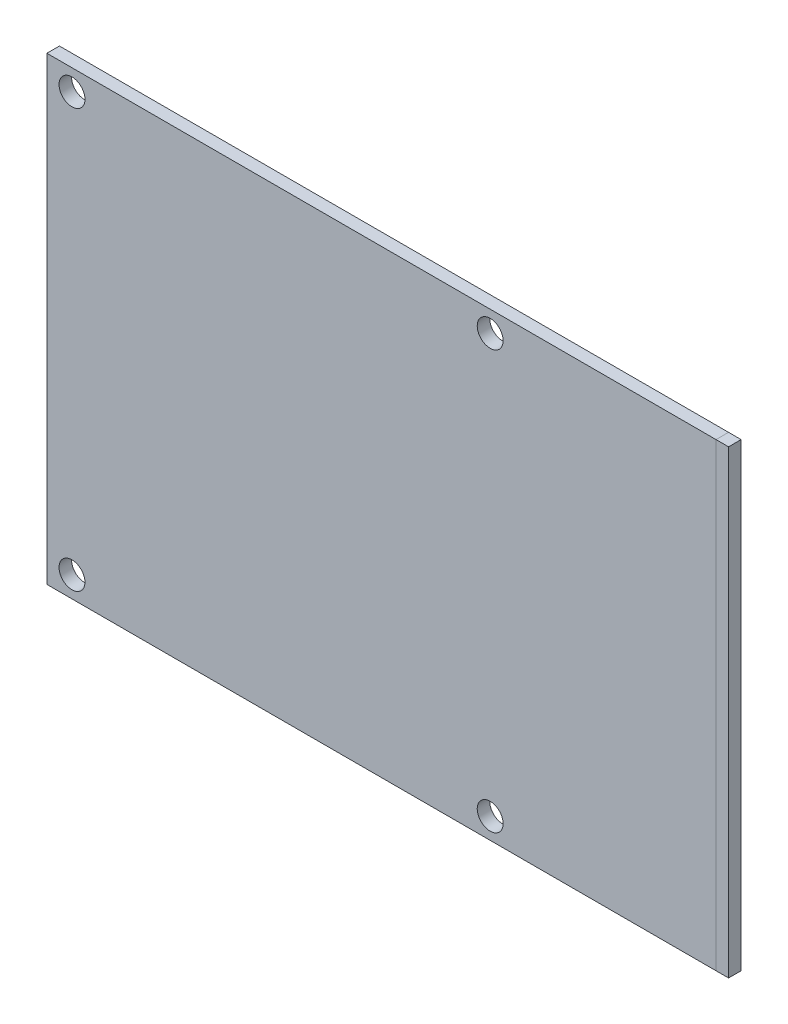
SolidWorks part; units mm, degrees
material "PTFE(普通)"
ref_plane "前视基准面" through (0, 0, 0) normal (0, 0, 1) x (1, 0, 0)
ref_plane "上视基准面" through (0, 0, 0) normal (0, 1, 0) x (1, 0, 0)
ref_plane "右视基准面" through (0, 0, 0) normal (1, 0, 0) x (0, 0, -1)
other "Configuration Table"
sketch "草图1" plane through (0, 0, 0) normal (0, 0, 1) x (1, 0, 0)
  line L1 (40, -27.5) -> (-40, -27.5)
  line L2 (40, -27.5) -> (40, 27.5)
  line L3 (40, 27.5) -> (-40, 27.5)
  line L4 (-40, -27.5) -> (-40, 27.5)
  line L5 (40, -27.5) -> (-40, 27.5) construction
  line L6 (40, 27.5) -> (-40, -27.5) construction
  point P0 (0, 0)
  dimension "D1" = 40
  dimension "D2" = 27.5
extrude "凸台-拉伸1" add sketch "草图1" along normal blind 1.5
sketch "草图2" plane through (0, 0, 0) normal (0, 0, -1) x (-1, 0, 0)
  line L0 (-40, 27.5) -> (40, 27.5) construction
  line L1 (40, -27.5) -> (-40, -27.5) construction
  line L2 (40, 27.5) -> (40, -27.5) construction
  line L3 (37, 25) -> (37, -25) construction
  circle A0 centre (37, 25) radius 1.55
  circle A1 centre (37, -25) radius 1.55
  circle A2 centre (-13, 25) radius 1.55
  circle A3 centre (-13, -25) radius 1.55
  dimension "D1" = 3.1
  dimension "D2" = 3.1
  dimension "D3" = 3.1
  dimension "D4" = 3.1
  dimension "D5" = 2.5
  dimension "D6" = 2.5
  dimension "D7" = 3
  dimension "D8" = 50
extrude "切除-拉伸1" cut sketch "草图2" against normal blind 1.5 contours A3 | A1 | A0 | A2
sketch "草图3" plane through (40, 0, 0) normal (1, 0, 0) x (0, 0, -1)
  line L1 (-1.5, 27.5) -> (0, 27.5)
  line L2 (-1.5, 27.5) -> (-1.5, -27.5)
  line L3 (-1.5, -27.5) -> (0, -27.5)
  line L4 (0, 27.5) -> (0, -27.5)
extrude "凸台-拉伸2" add sketch "草图3" along normal blind 1.5 separate body
sketch "草图4" plane through (0, 0, 1.5) normal (0, 0, 1) x (1, 0, 0)
  line L0 (40, 0) -> (41.5, 0) construction
  line L1 (40, -27.5) -> (40, 27.5) construction
  line L2 (41.5, 27.5) -> (41.5, -27.5) construction
  line L3 (41.5, 0) -> (78.8132, 0) construction
  arc A0 (64.867, -41.3292) -> (63.9116, 40.7906) centre (87.5351, 0) cw
  dimension "D1" = 37.3132
